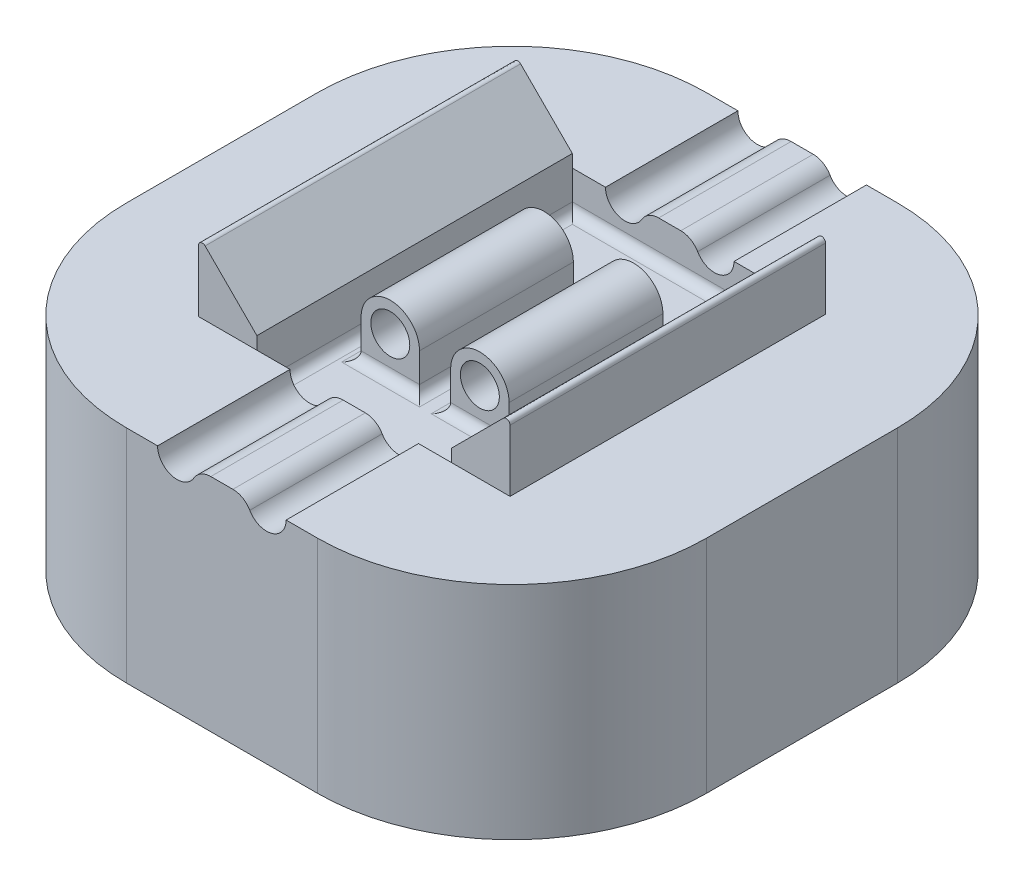
SolidWorks part; units mm, degrees
ref_plane "Front Plane" through (0, 0, 0) normal (0, 0, 1) x (1, 0, 0)
ref_plane "Top Plane" through (0, 0, 0) normal (0, 1, 0) x (1, 0, 0)
ref_plane "Right Plane" through (0, 0, 0) normal (1, 0, 0) x (0, 0, -1)
sketch "Sketch2" plane through (0, 0, 0) normal (0, 1, 0) x (1, 0, 0)
  line L0 (-14.9, 14.9) -> (14.9, 14.9)
  line L1 (-15, -15) -> (15, -15)
  line L2 (-15, -15) -> (-15, 15)
  line L3 (-15, 15) -> (15, 15)
  line L4 (15, -15) -> (15, 15)
  line L5 (-15, -15) -> (15, 15) construction
  line L6 (-15, 15) -> (15, -15) construction
  line L7 (14.9, -14.9) -> (14.9, 14.9)
  line L8 (-14.9, -14.9) -> (14.9, -14.9)
  line L9 (-14.9, -14.9) -> (-14.9, 14.9)
  point P0 (0, 0)
  dimension "D1" = 30
  dimension "D2" = 30
  dimension "D3" = 0.1
extrude "Boss-Extrude1" add sketch "Sketch2" along normal blind 6.35 contours L9 L8 L7 L0 region at (0, 0, 0)
sketch "Sketch3" plane through (0, 6.35, 0) normal (0, 1, 0) x (1, 0, 0)
  line L5 (-14.9, -14.9) -> (14.9, -14.9) construction
  line L6 (14.9, -14.9) -> (14.9, 14.9) construction
  line L16 (-14.9, 14.9) -> (14.9, 14.9) construction
  line L17 (-14.9, -14.9) -> (-14.9, 14.9) construction
  line L18 (-14.9, 14.9) -> (14.9, 14.9)
  line L19 (14.9, -14.9) -> (14.9, 14.9)
  line L20 (-14.9, -14.9) -> (14.9, -14.9)
  line L21 (-14.9, -14.9) -> (-14.9, 14.9)
  point P2 (0, 0)
extrude "Boss-Extrude2" add sketch "Sketch3" along normal blind 5
fillet "Fillet1" radius 10 4 edges at (-14.9, 5.675, -14.9) (14.9, 5.675, -14.9) (14.9, 5.675, 14.9) (-14.9, 5.675, 14.9)
sketch "Sketch5" plane through (0, 11.35, 0) normal (0, 1, 0) x (1, 0, 0)
  line L1 (-5, -8.1) -> (5, -8.1)
  line L2 (-5, -8.1) -> (-5, 8.1)
  line L3 (-5, 8.1) -> (5, 8.1)
  line L4 (5, -8.1) -> (5, 8.1)
  line L5 (-5, -8.1) -> (5, 8.1) construction
  line L6 (-5, 8.1) -> (5, -8.1) construction
  point P0 (0, 0)
  dimension "D1" = 16.2
  dimension "D2" = 10
extrude "Cut-Extrude1" cut sketch "Sketch5" against normal blind 2
sketch "Sketch4" plane through (0, 11.35, 0) normal (0, 1, 0) x (1, 0, 0)
  line L0 (0, 14.9) -> (0, -14.9)
  line L1 (-4.9, -14.9) -> (4.9, -14.9) construction
  line L2 (4.9, 14.9) -> (-4.9, 14.9) construction
  line L5 (-2.3, 3.95) -> (-2.3, -3.95)
  line L6 (-3.8, -3.95) -> (-0.8, -3.95)
  line L7 (-3.8, -3.95) -> (-3.8, 3.95)
  line L8 (-3.8, 3.95) -> (-0.8, 3.95)
  line L9 (-0.8, -3.95) -> (-0.8, 3.95)
  line L10 (-3.8, -3.95) -> (-0.8, 3.95) construction
  line L11 (-3.8, 3.95) -> (-0.8, -3.95) construction
  line L12 (3.8, -3.95) -> (-0.8, -3.95)
  line L13 (3.8, -3.95) -> (3.8, 3.95)
  line L14 (2.3, 3.95) -> (2.3, -3.95)
  line L15 (3.8, 3.95) -> (-0.8, 3.95)
  point P2 (0, -14.9)
  point P5 (0, 14.8588)
  point P6 (-2.3, 0)
  point P13 (0, 0)
  point P18 (0, 14.9)
  dimension "D1" = 2.3
  dimension "D2" = 3
  dimension "D3" = 7.9
revolve "Revolve1" add sketch "Sketch4" angle 360 about L5 region at (-3.05, 11.35, 0)
revolve "Revolve2" add sketch "Sketch4<4>" angle 360 about L14 region at (3.05, 11.35, 0)
sketch "Sketch4<4>" plane through (0, 11.35, 0) normal (0, 1, 0) x (1, 0, 0) same geometry as "Sketch4"
sketch "Sketch6" plane through (0, 0, 3.95) normal (0, 0, 1) x (1, 0, 0)
  line L0 (-3.8, 11.35) -> (-3.8, 6.35)
  line L1 (-0.8, 11.35) -> (-0.8, 6.35)
  line L2 (0.8, 11.35) -> (0.8, 6.35)
  line L3 (3.8, 11.35) -> (3.8, 6.35)
  line L4 (-3.8, 6.35) -> (3.8, 6.35)
  line L5 (-3.8, 11.35) -> (3.8, 11.35)
  circle A0 centre (-2.3, 11.35) radius 1.5 construction
  circle A1 centre (2.3, 11.35) radius 1.5 construction
  circle M5 centre (-2.3, 11.35) radius 1.5
  dimension "D1" = 5
extrude "Boss-Extrude3" add sketch "Sketch6" against normal up to surface (7.9 mm away) contours L0 L4 L1 M5 | L5 L2 L4 L3 | L5 M5 region at (-2.3, 8.2756, 3.95) region at (-2.3, 10.7134, 3.95) region at (2.3, 8.85, 3.95) up to face at (0.8, 11.35, -3.95)
fillet "Fillet3" radius 0.5 12 edges at (0, 9.35, 8.1) (-5, 9.35, 0) (0, 9.35, -8.1) (5, 9.35, 0) (-2.3, 9.35, 3.95) (-0.8, 9.35, 0) (-2.3, 9.35, -3.95) (-3.8, 9.35, 0) (2.3, 9.35, -3.95) (0.8, 9.35, 0) (2.3, 9.35, 3.95) (3.8, 9.35, 0)
sketch "Sketch7" plane through (0, 0, 3.95) normal (0, 0, 1) x (1, 0, 0)
  circle A0 centre (2.3, 11.35) radius 1
  circle A1 centre (-2.3, 11.35) radius 1
  dimension "D1" = 2
  dimension "D2" = 2
extrude "Cut-Extrude2" cut sketch "Sketch7" against normal through all and the other way through all
sketch "Sketch8" plane through (0, 0, 0) normal (0, -1, 0) x (1, 0, 0)
  circle A0 centre (0, 0) radius 2.125
  dimension "D1" = 4.25
extrude "Cut-Extrude3" cut sketch "Sketch8" against normal blind 5 contours A0 region at (0, 0, 0)
sketch "Sketch9" plane through (0, 11.35, 0) normal (0, 1, 0) x (1, 0, 0)
  line L0 (0, -7.0675) -> (0, 7.0675) construction
  line L1 (5, -8.1) -> (8, -8.1)
  line L2 (5, -8.1) -> (5, 8.1)
  line L3 (5, 8.1) -> (8, 8.1)
  line L4 (8, -8.1) -> (8, 8.1)
  line L5 (-5, -8.1) -> (-8, -8.1)
  line L6 (-5, 8.1) -> (-8, 8.1)
  line L7 (-8, -8.1) -> (-8, 8.1)
  line L8 (-5, 8.1) -> (-5, -8.1) construction
  line L9 (-5, 8.1) -> (-5, -8.1)
  point P5 (0, 0)
  line M12 (5, 8.1) -> (5, -8.1)
  dimension "D1" = 3
extrude "Boss-Extrude4" add sketch "Sketch9" along normal blind 0.65 contours L9 L6 L7 L5 | L1 L4 L3 M12 region at (6.5, 11.35, 0) region at (-6.5, 11.35, 0)
sketch "Sketch10" plane through (0, 0, 8.1) normal (0, 0, 1) x (1, 0, 0)
  line L0 (5, 12) -> (8, 15)
  line L1 (8, 15) -> (8, 12)
  line L2 (5, 12) -> (8, 12) construction
  line L4 (5, 12) -> (8, 12)
  line L5 (0, -7.0675) -> (0, 7.0675) construction
  line L6 (-5, 12) -> (-8, 12)
  line L7 (-5, 12) -> (-8, 15)
  line L8 (5, 11.35) -> (8, 11.35)
  line L9 (8, 11.35) -> (8, 12)
  line L10 (8, 12) -> (5, 12)
  line L11 (5, 12) -> (5, 11.35)
  line L12 (5, 11.35) -> (8, 11.35)
  line L13 (8, 11.35) -> (8, 12)
  line L15 (5, 12) -> (5, 11.35)
  line L16 (-8, 15) -> (-8, 12)
  line M9 (8, 12) -> (5, 12)
  dimension "D1" = 45
  dimension "D2" = 0
extrude "Boss-Extrude5" add sketch "Sketch10" against normal up to surface (16.2 mm away) contours L1 L0 M9 | L7 L16 L6 region at (7, 13, 8.1) region at (-7, 13, 8.1) up to face at (6.5, 11.675, -8.1)
fillet "Fillet4" radius 0.2 2 edges at (-8, 15, 0) (8, 15, 0)
fillet "Fillet5" radius 1 4 edges at (1.3, 11.35, -11.5) (-1.3, 11.35, -11.5) (1.3, 11.35, 11.5) (-1.3, 11.35, 11.5)
